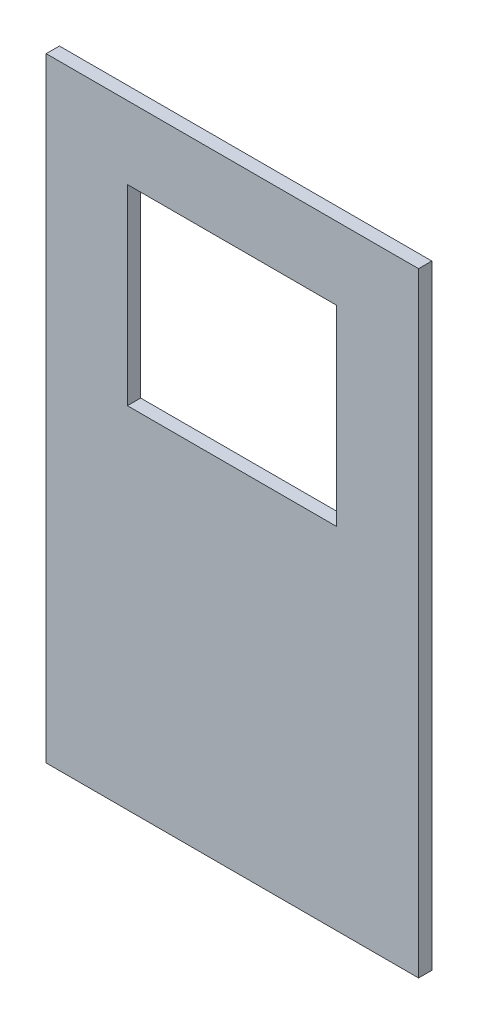
SolidWorks part; units mm, degrees
ref_plane "Front Plane" through (0, 0, 0) normal (0, 0, 1) x (1, 0, 0)
ref_plane "Top Plane" through (0, 0, 0) normal (0, 1, 0) x (1, 0, 0)
ref_plane "Right Plane" through (0, 0, 0) normal (1, 0, 0) x (0, 0, -1)
sketch "Sketch1" plane through (0, 0, 0) normal (0, 0, 1) x (1, 0, 0)
  line L0 (0.1058, 73.6301) -> (-0.0148, 62.4901) construction
  line L1 (-0.0148, 62.4901) -> (-0.0148, 56.2001) construction
  line L2 (-0.0148, 56.2001) -> (-0.0148, 10.268) construction
  line L3 (-15.4692, -49.8142) -> (-8.5409, -45.8142) construction
  line L4 (-15.4692, -49.8142) -> (0.5308, -49.8142) construction
  line L5 (0.5308, -49.8142) -> (7.4591, -45.8142) construction
  line L6 (-0.0148, 10.268) -> (0.1058, -73.6642) construction
  line L15 (-16.3293, -29.1587) -> (-16.3293, -23.8757)
  line L20 (-0.2968, -48.3429) -> (6.6759, -44.4208)
  line L21 (8.2583, -47.1985) -> (1.3584, -51.2855)
  line L22 (-44.5392, 73.6301) -> (44.7508, 73.6301)
  line L23 (44.7508, 73.6301) -> (44.7508, -73.6642)
  line L24 (44.7508, -73.6642) -> (-44.5392, -73.6642)
  line L25 (-44.5392, -73.6642) -> (-44.5392, 73.6301)
  line L26 (-25.0598, 56.2001) -> (-25.0598, 10.268)
  line L27 (-25.0598, 10.268) -> (25.0303, 10.268)
  line L28 (25.0303, 10.268) -> (25.0303, 56.2001)
  line L29 (25.0303, 56.2001) -> (-25.0598, 56.2001)
  line L34 (35.8896, 62.4901) -> (-35.9192, 62.4901)
  line L35 (-38.4192, 59.9901) -> (-38.4192, 6.918)
  line L36 (-35.9192, 4.418) -> (29.9974, 4.418)
  line L37 (38.3896, 13.668) -> (38.3896, 59.9901)
  line L38 (-16.2968, -48.3429) -> (-9.3241, -44.4208)
  line L39 (-7.7417, -47.1985) -> (-14.6416, -51.2855)
  line L150 (42.2525, -55.0539) -> (42.2511, -54.9499)
  circle A2 centre (-26.9008, -26.5172) radius 3.6
  arc A3 (8.2583, -47.1985) -> (6.6759, -44.4208) centre (7.4591, -45.8142) ccw
  arc A6 (-16.2968, -48.3429) -> (-14.6416, -51.2855) centre (-15.4692, -49.8142) ccw
  arc A7 (-7.7417, -47.1985) -> (-9.3241, -44.4208) centre (-8.5409, -45.8142) ccw
  circle A15 centre (18.9576, -29.5613) radius 3.5
  circle A16 centre (33.0683, -21.4917) radius 3.5
  arc A17 (-0.2968, -48.3429) -> (1.3584, -51.2855) centre (0.5308, -49.8142) ccw
  circle A19 centre (-32.8459, 40.326) radius 4.5
  arc A24 (38.3896, 59.9901) -> (35.8896, 62.4901) centre (35.8896, 59.9901) ccw
  arc A25 (-35.9192, 62.4901) -> (-38.4192, 59.9901) centre (-35.9192, 59.9901) ccw
  arc A26 (-38.4192, 6.918) -> (-35.9192, 4.418) centre (-35.9192, 6.918) ccw
  arc A27 (29.9974, 4.418) -> (38.3896, 13.668) centre (29.1397, 13.6282) ccw
  dimension "D4" = 11.14
  dimension "D8" = 7
  dimension "D11" = 9
  dimension "D12" = 7.2
  dimension "D14" = 9.25
  dimension "D15" = 2.5
  dimension "D2" = 89.29
  dimension "D3" = 147.2943
  dimension "D5" = 25.9097
  dimension "D6" = 8.0696
  dimension "D7" = 14.1107
  dimension "D9" = 7.7861
  dimension "D10" = 22.1641
  dimension "D13" = 10.5715
  dimension "D16" = 6.29
  dimension "D17" = 6.12
  dimension "D18" = 5.85
  dimension "D19" = 16
  dimension "D20" = 8
  dimension "D21" = 29.07
  dimension "D22" = 23.85
  dimension "D23" = 30
extrude "Bezel" add sketch "Sketch1<6>" along normal blind 3.18 contours L36 A27 L37 A24 L34 A25 L35 A26 L29 L28 L27 L26 A19 region at (36.9765, 61.077, 0)
sketch "Sketch1<6>" plane through (0, 0, 0) normal (0, 0, 1) x (1, 0, 0) same geometry as "Sketch1"
extrude "Body" add sketch "Sketch1<7>" along normal blind 3.18 contours L25 L24 L23 L22 A27 L36 A26 L35 A25 L34 A24 L37 A17 L20 A3 L21 A16 A15 A7 L39 A6 L38 A2 region at (0.1688, -16.746, 0)
sketch "Sketch1<7>" plane through (0, 0, 0) normal (0, 0, 1) x (1, 0, 0) same geometry as "Sketch1"
extrude "Buttons" add sketch "Sketch1" along normal blind 3.18 contours A19 | A2 | L39 A7 L38 A6 | L20 A17 L21 A3 | A15 | A16 region at (3.913, -47.8614, 0) region at (-12.087, -47.8614, 0) region at (-26.9008, -26.5172, 0) region at (18.9576, -29.5613, 0) region at (33.0683, -21.4917, 0) region at (-32.8459, 40.326, 0)
